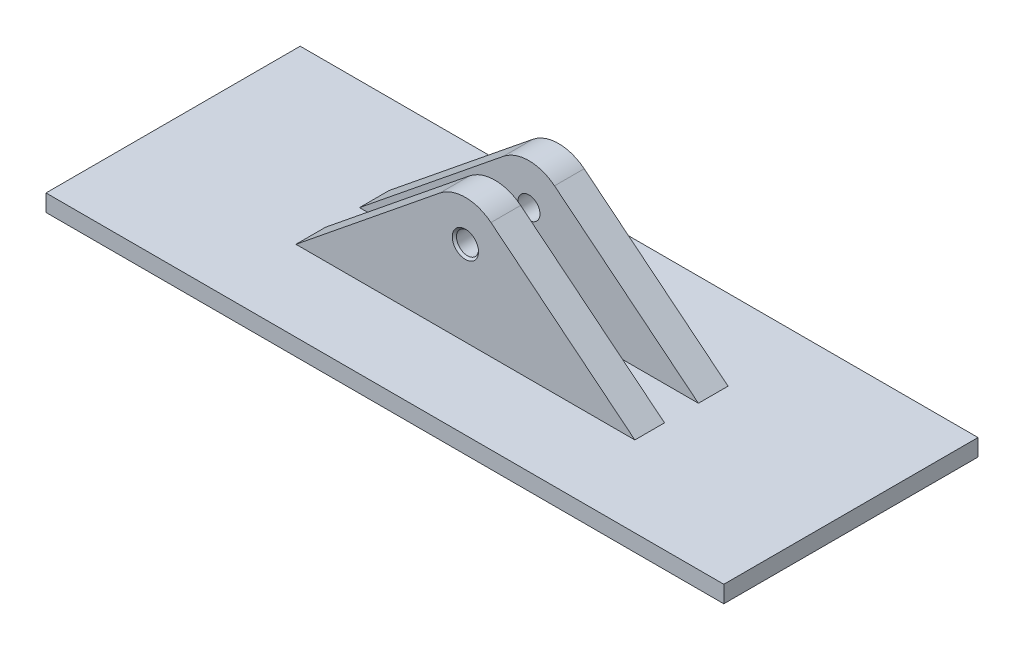
SolidWorks part; units mm, degrees
ref_plane "Front Plane" through (0, 0, 0) normal (0, 0, 1) x (1, 0, 0)
ref_plane "Top Plane" through (0, 0, 0) normal (0, 1, 0) x (1, 0, 0)
ref_plane "Right Plane" through (0, 0, 0) normal (1, 0, 0) x (0, 0, -1)
sketch "Sketch1" plane through (0, 0, 0) normal (0, 0, 1) x (1, 0, 0)
  line L0 (-6.0364, 7.4647) -> (-40, -20)
  line L1 (-40, -20) -> (40, -20)
  line L2 (40, -20) -> (6.0364, 7.4647)
  circle A0 centre (0, 0) radius 2.6
  arc A1 (6.0364, 7.4647) -> (-6.0364, 7.4647) centre (0, 0) ccw
  point P6 (0, -20)
  dimension "D1" = 5.2
  dimension "D2" = 7
  dimension "D3" = 80
  dimension "D4" = 20
extrude "Boss-Extrude1" add sketch "Sketch1" along normal blind 22
sketch "Sketch2" plane through (0, -20, 0) normal (0, -1, 0) x (-1, 0, 0)
  line L0 (-40, -22) -> (-40, 0) construction
  line L1 (-80, -41) -> (80, -41)
  line L2 (-80, -41) -> (-80, 19)
  line L3 (-80, 19) -> (80, 19)
  line L4 (80, -41) -> (80, 19)
  point P6 (-40, -11)
  point P7 (-80, -11)
  point P9 (0, 19)
  dimension "D1" = 160
  dimension "D2" = 60
extrude "Boss-Extrude2" add sketch "Sketch2" along normal blind 4
sketch "Sketch3" plane through (80, 0, 0) normal (1, 0, 0) x (0, 0, -1)
  line L0 (19, -20) -> (-41, -20) construction
  line L1 (-15, -20) -> (-7, -20)
  line L2 (-15, -20) -> (-15, 15)
  line L3 (-15, 15) -> (-7, 15)
  line L4 (-7, -20) -> (-7, 15)
  line L5 (0, -20) -> (0, 7.4647) construction
  dimension "D1" = 8
  dimension "D2" = 7
  dimension "D3" = 35
extrude "Cut-Extrude1" cut sketch "Sketch3" against normal through all
chamfer "Chamfer1" distance 0.5 angle 45 2 edges at (2.6, 0, 22) (2.6, 0, 0)
